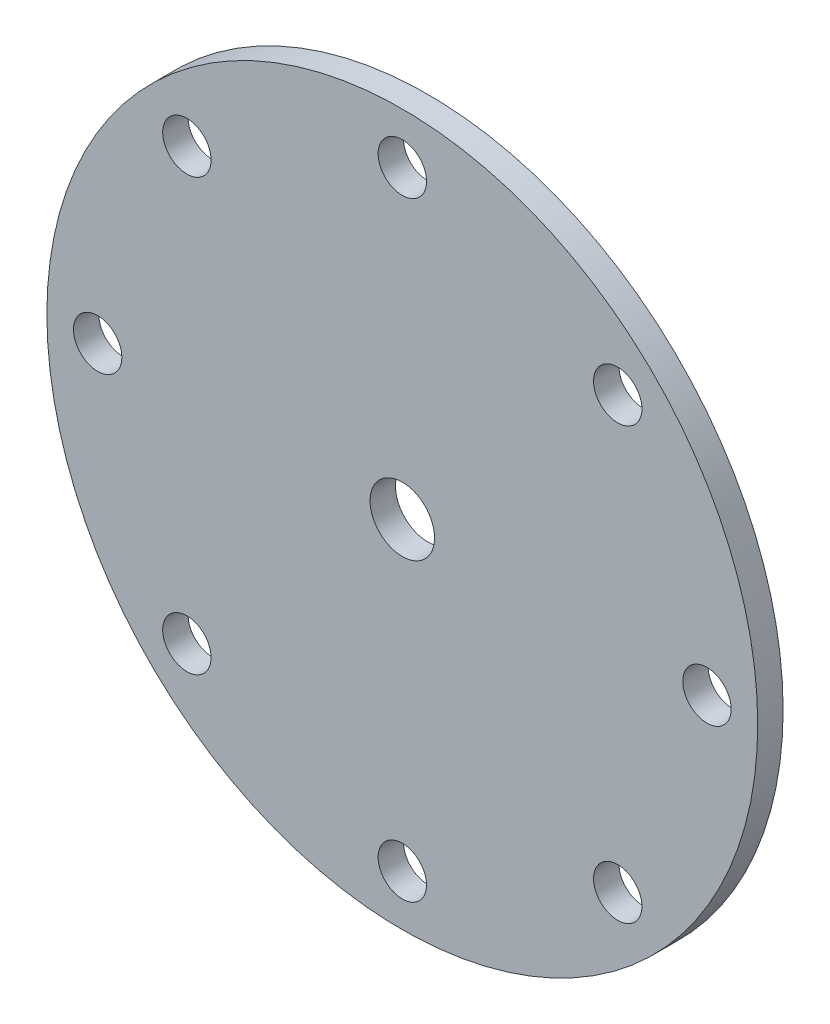
SolidWorks part; units mm, degrees
ref_plane "Front Plane" through (0, 0, 0) normal (0, 0, 1) x (1, 0, 0)
ref_plane "Top Plane" through (0, 0, 0) normal (0, 1, 0) x (1, 0, 0)
ref_plane "Right Plane" through (0, 0, 0) normal (1, 0, 0) x (0, 0, -1)
sketch "Sketch1" plane through (0, 0, 0) normal (0, 0, 1) x (1, 0, 0)
  line L0 (0, 70) -> (0, -70) construction
  line L1 (-70, 0) -> (70, 0) construction
  line L2 (-42.4264, 42.4264) -> (42.4264, -42.4264) construction
  line L3 (-42.4264, -42.4264) -> (42.4264, 42.4264) construction
  circle A0 centre (0, 0) radius 70
  circle A1 centre (0, 0) radius 6.35
  circle A2 centre (0, 60) radius 4.7625
  circle A6 centre (42.4264, 42.4264) radius 4.7625
  circle A7 centre (60, 0) radius 4.7625
  circle A8 centre (42.4264, -42.4264) radius 4.7625
  circle A9 centre (0, -60) radius 4.7625
  circle A10 centre (-42.4264, -42.4264) radius 4.7625
  circle A11 centre (-60, 0) radius 4.7625
  circle A12 centre (-42.4264, 42.4264) radius 4.7625
  dimension "D1" = 140
  dimension "D2" = 12.7
  dimension "D3" = 9.525
  dimension "D6" = 10
  dimension "D4" = 10
  dimension "D5" = 8
extrude "Rotor Disc" add sketch "Sketch1" along normal blind 5 contours A0 A12 A11 A10 A8 A7 A6 A1 A2 region at (-68.0201, 0, 0)
